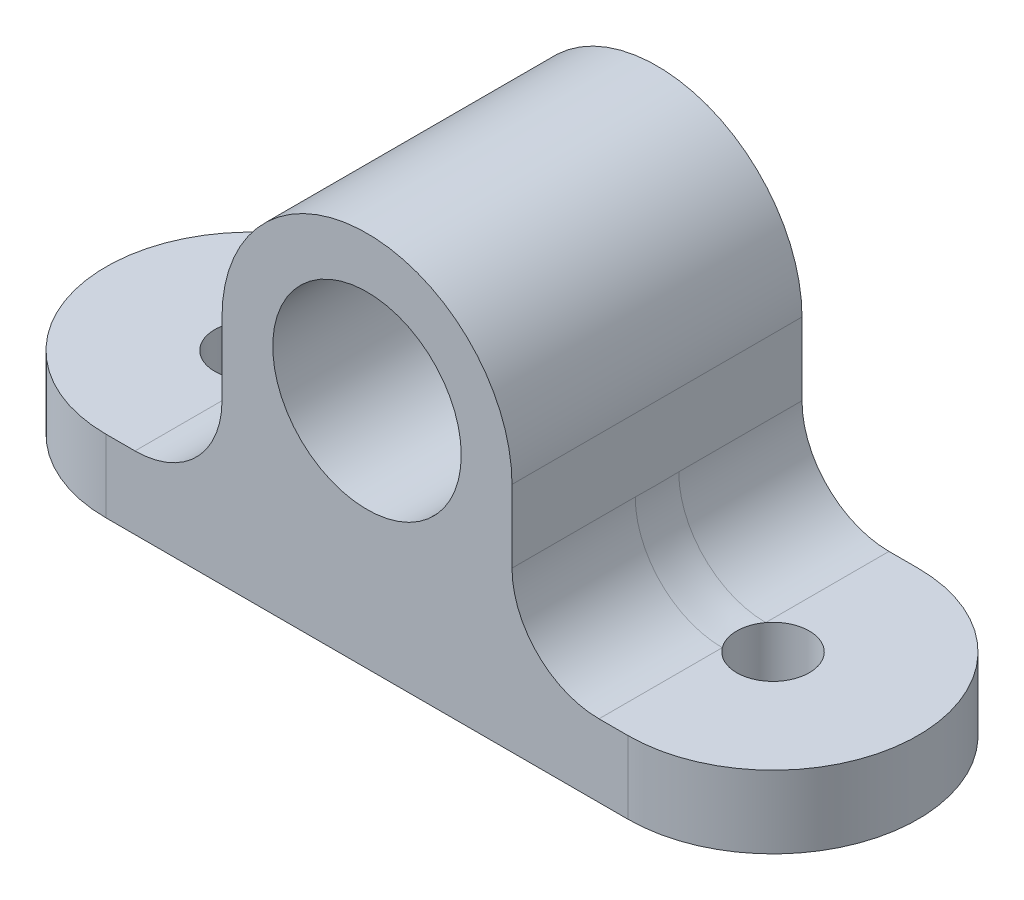
SolidWorks part; units mm, degrees
ref_plane "Piano frontale" through (0, 0, 0) normal (0, 0, 1) x (1, 0, 0)
ref_plane "Piano superiore" through (0, 0, 0) normal (0, 1, 0) x (1, 0, 0)
ref_plane "Piano destro" through (0, 0, 0) normal (1, 0, 0) x (0, 0, -1)
sketch "Schizzo1" plane through (0, 0, 0) normal (0, 1, 0) x (1, 0, 0)
  line L1 (0, 0) -> (36, 0)
  line L3 (0, -20) -> (36, -20)
  arc A0 (36, 0) -> (36, -20) centre (36, -10) cw
  arc A1 (0, 0) -> (0, -20) centre (0, -10) ccw
  dimension "D2" = 10
  dimension "D1" = 36
extrude "Estrusione-Estrusione1" add sketch "Schizzo1" along normal blind 5 contours L1 A0 L3 A1
sketch "Schizzo2" plane through (0, 5, 0) normal (0, 1, 0) x (1, 0, 0)
  line L0 (18, 0) -> (18, -20) construction
  line L1 (0, 0) -> (36, 0) construction
  line L2 (0, -20) -> (36, -20) construction
  line L3 (28, 0) -> (8, 0)
  line L4 (8, 0) -> (8, -20)
  line L5 (8, -20) -> (28, -20)
  line L6 (28, 0) -> (28, -20)
  dimension "D1" = 20
extrude "Estrusione-Estrusione2" add sketch "Schizzo2" along normal blind 21
sketch "Schizzo3" plane through (0, 0, 20) normal (0, 0, 1) x (1, 0, 0)
  line L0 (28, 5) -> (36, 5) construction
  line L1 (28, 26) -> (28, 5) construction
  line L2 (8, 26) -> (18, 26)
  line L3 (28, 26) -> (28, 16)
  line L5 (28, 26) -> (18, 26)
  line L6 (8, 26) -> (8, 16)
  circle A0 centre (18, 16) radius 10
  dimension "D3" = 20
  dimension "D1" = 11
  dimension "D2" = 10
fillet "Raccordo1" 2 edges at (8, 26, 10) (28, 26, 10) type full round first side face at (8, 15.5, 10) second side face at (28, 15.5, 10) middle face at (18, 26, 10)
sketch "Schizzo5" plane through (0, 0, 20) normal (0, 0, 1) x (1, 0, 0)
  circle A0 centre (18, 16) radius 6.5
  arc A1 (28, 16) -> (8, 16) centre (18, 16) ccw construction
  dimension "D1" = 13
extrude "Taglio-Estrusione4" cut sketch "Schizzo5" against normal through all contours A0
sketch "Schizzo6" plane through (0, 5, 0) normal (0, 1, 0) x (1, 0, 0)
  circle A0 centre (0, -10) radius 2.5
  circle A1 centre (36, -10) radius 2.5
  arc A2 (0, 0) -> (0, -20) centre (0, -10) ccw construction
  dimension "D2" = 5
  dimension "D1" = 36
extrude "Taglio-Estrusione5" cut sketch "Schizzo6" against normal through all
fillet "Raccordo2" radius 6 2 edges at (28, 5, 10) (8, 5, 10)
